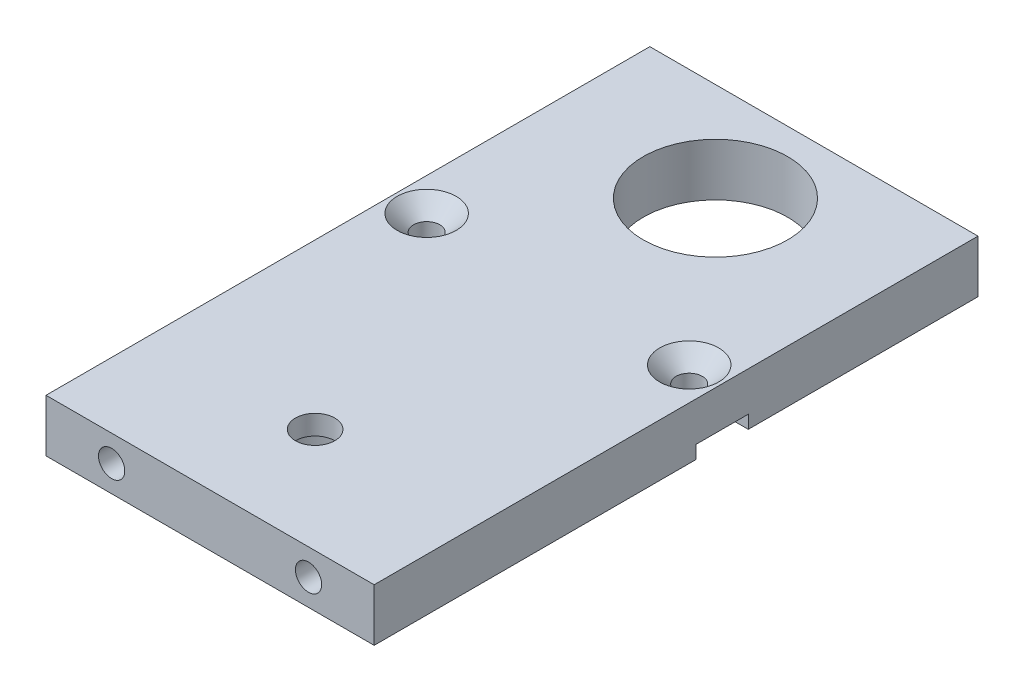
SolidWorks part; units mm, degrees
material "PVC rigide"
ref_plane "Plan de face" through (0, 0, 0) normal (0, 0, 1) x (1, 0, 0)
ref_plane "Plan de dessus" through (0, 0, 0) normal (0, 1, 0) x (1, 0, 0)
ref_plane "Plan de droite" through (0, 0, 0) normal (1, 0, 0) x (0, 0, -1)
sketch "Esquisse1" plane through (0, 0, 0) normal (0, 1, 0) x (1, 0, 0)
  line L0 (-6.4914, -72.1179) -> (-6.4914, 19.8821) construction
  line L1 (-31.4914, 19.8821) -> (18.5086, 19.8821)
  line L2 (-31.4914, 19.8821) -> (-31.4914, -72.1179)
  line L3 (-31.4914, -72.1179) -> (18.5086, -72.1179)
  line L4 (18.5086, 19.8821) -> (18.5086, -72.1179)
  line L6 (-41.3411, -19.1179) -> (33.4874, -19.1179) construction
  circle A1 centre (-6.4914, 4.8821) radius 11
  circle A2 centre (-26.4914, -19.1179) radius 2
  circle A3 centre (13.5086, -19.1179) radius 2
  dimension "D5" = 22
  dimension "D10" = 4
  dimension "D1" = 50
  dimension "D2" = 92
  dimension "D6" = 15
  dimension "D7" = 53
  dimension "D8" = 5
  dimension "D9" = 5
extrude "Boss.-Extru.1" add sketch "Esquisse1" along normal blind 8
chamfer "Chanfrein1" distance 2.5 angle 45 2 edges at (13.5086, 8, 21.1179) (-26.4914, 8, 21.1179)
sketch "Esquisse2" plane through (0, 0, 72.1179) normal (0, 0, 1) x (1, 0, 0)
  line L0 (-31.4914, 4) -> (18.5086, 4) construction
  line L1 (-31.4914, 8) -> (-31.4914, 0) construction
  line L2 (18.5086, 8) -> (18.5086, 0) construction
  circle A0 centre (-21.4914, 4) radius 2
  circle A1 centre (8.5086, 4) radius 2
  dimension "D1" = 4
  dimension "D2" = 10
  dimension "D3" = 10
extrude "Enlèv. mat.-Extru.1" cut sketch "Esquisse2" against normal blind 10
sketch "Esquisse3" plane through (0, 0, 0) normal (0, -1, 0) x (1, 0, 0)
  line L0 (-31.4914, 56.1179) -> (18.5086, 56.1179) construction
  line L1 (-31.4914, -19.8821) -> (-31.4914, 72.1179) construction
  line L2 (18.5086, 72.1179) -> (18.5086, -19.8821) construction
  line L3 (-31.4914, 72.1179) -> (18.5086, 72.1179) construction
  circle A0 centre (-6.4914, 56.1179) radius 8
  dimension "D2" = 16
  dimension "D1" = 16
extrude "Enlèv. mat.-Extru.2" cut sketch "Esquisse3" against normal blind 5
sketch "Esquisse4" plane through (0, 5, 0) normal (0, -1, 0) x (1, 0, 0)
  circle A0 centre (-6.4914, 56.1179) radius 3
  circle A1 centre (-6.4914, 56.1179) radius 8 construction
  dimension "D1" = 6
extrude "Enlèv. mat.-Extru.3" cut sketch "Esquisse4" against normal through all
sketch "Esquisse5" plane through (0, 0, 0) normal (0, -1, 0) x (1, 0, 0)
  line L0 (18.5086, 72.1179) -> (18.5086, -19.8821) construction
  line L1 (18.5086, 15.1179) -> (-31.4914, 15.1179)
  line L2 (18.5086, 15.1179) -> (18.5086, 23.1179)
  line L3 (18.5086, 23.1179) -> (-31.4914, 23.1179)
  line L4 (-31.4914, 15.1179) -> (-31.4914, 23.1179)
  circle A0 centre (13.5086, 19.1179) radius 2 construction
  dimension "D1" = 4
  dimension "D2" = 8
extrude "Enlèv. mat.-Extru.4" cut sketch "Esquisse5" against normal blind 2
